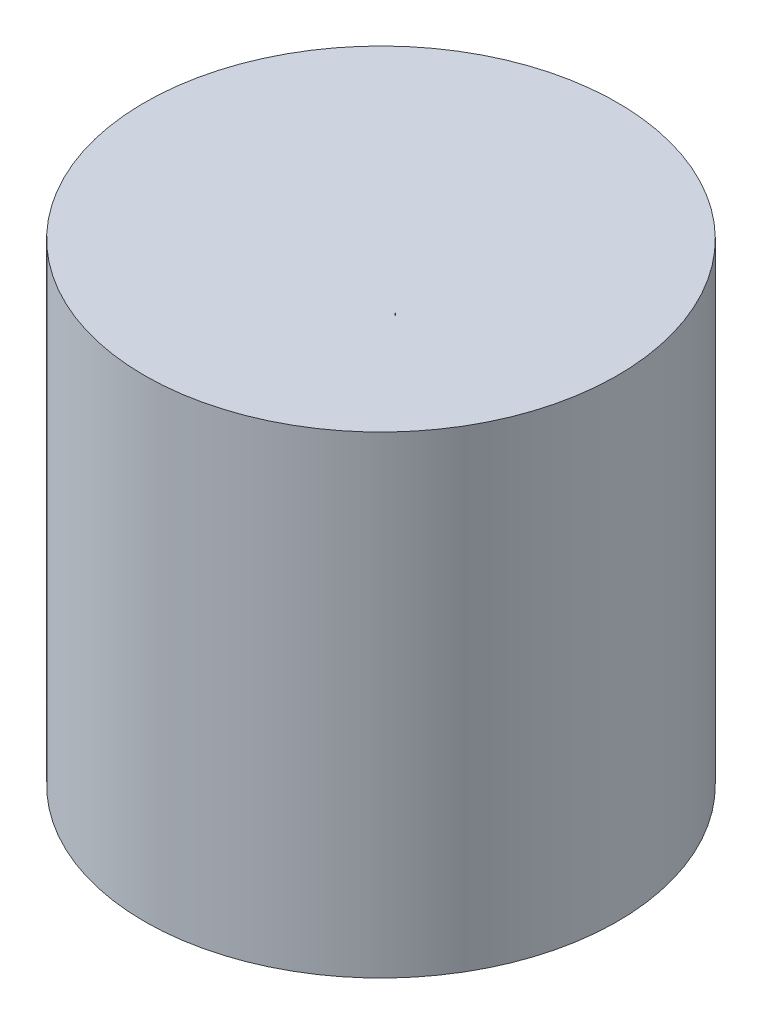
SolidWorks part; units mm, degrees
ref_plane "Front Plane" through (0, 0, 0) normal (0, 0, 1) x (1, 0, 0)
ref_plane "Top Plane" through (0, 0, 0) normal (0, 1, 0) x (1, 0, 0)
ref_plane "Right Plane" through (0, 0, 0) normal (1, 0, 0) x (0, 0, -1)
sketch "Sketch2" plane through (0, 0, 0) normal (0, 1, 0) x (1, 0, 0)
  line L0 (0.1758, -2.2335) -> (0.1763, -2.2335)
  line L2 (-2.1888, 2.9614) -> (-2.1888, -2.2335)
  line L4 (2.2036, 2.9614) -> (2.2036, -2.2335)
  line L6 (-0.246, -2.2335) -> (-0.246, -0.4828)
  line L7 (-0.246, -0.4828) -> (0.1758, -0.4828)
  line L8 (0.1758, -2.2335) -> (0.1758, -0.4828)
  circle A0 centre (0, 0) radius 6.35
  arc A1 (-2.1888, -2.2335) -> (-0.246, -2.2335) centre (-1.2174, -2.2335) ccw
  arc A2 (1.9674, -1.5831) -> (1.8844, -1.495) centre (1.19, -2.2335) ccw
  arc A3 (2.2036, 2.9614) -> (-2.1888, 2.9614) centre (0.0074, 2.9614) ccw
  circle A4 centre (0, 0) radius 5.9965
  arc A5 (0.1763, -2.2335) -> (2.2036, -2.2335) centre (1.19, -2.2335) ccw
  ellipse E0 centre (-2.0347, 3.7698) end of major axis (-3.3587, 3.7698) minor radius 0.6277
  ellipse E1 centre (2.2036, 0.364) end of major axis (2.2036, 2.4124) minor radius 0.7602 (1.8844, -1.495) -> (1.9674, -1.5831) ccw
  ellipse E2 centre (2.2036, 0.364) end of major axis (2.2036, 2.4124) minor radius 0.7602 (2.2036, -1.6845) -> (2.2036, 2.4124) ccw
  dimension "D1" = 12.7
extrude "Boss-Extrude5" add sketch "Sketch2" along normal blind 12.7 contours A0 A4 region at (-6.1704, 0, 0)
extrude "Boss-Extrude6" add sketch "Sketch2<5>" along normal blind 2.54 contours A4 E2 L4 A5 L0 L8 L7 L6 A1 L2 A3 E0 | E0 A3 L2 A1 L6 L7 L8 L0 A5 L4 E1 A2 | A3 E0 | A3 E0 | L4 E2 region at (0.0702, 0, -0.8225) region at (2.5265, 0, -0.364) region at (-1.4642, 0, -3.7178) region at (-2.567, 0, -3.8183) region at (-5.8269, 0, 0)
sketch "Sketch2<5>" plane through (0, 0, 0) normal (0, 1, 0) x (1, 0, 0) same geometry as "Sketch2"
extrude "Boss-Extrude7" add sketch "Sketch2<6>" along normal blind 3.81 contours L4 E2 region at (2.5265, 0, -0.364)
sketch "Sketch2<6>" plane through (0, 0, 0) normal (0, 1, 0) x (1, 0, 0) same geometry as "Sketch2"
extrude "Boss-Extrude8" add sketch "Sketch2<7>" along normal blind 5.08 contours E0 A3 L2 A1 L6 L7 L8 L0 A5 L4 E1 A2 region at (0.0702, 0, -0.8225)
sketch "Sketch2<7>" plane through (0, 0, 0) normal (0, 1, 0) x (1, 0, 0) same geometry as "Sketch2"
extrude "Boss-Extrude9" add sketch "Sketch2<8>" along normal blind 6.35 contours A3 E0 | A3 E0 region at (-1.4642, 0, -3.7178) region at (-2.567, 0, -3.8183)
sketch "Sketch2<8>" plane through (0, 0, 0) normal (0, 1, 0) x (1, 0, 0) same geometry as "Sketch2"
extrude "Boss-Extrude12" add sketch "Sketch2<9>" along normal blind 12.7 contours A4 E2 L4 A5 L0 L8 L7 L6 A1 L2 A3 E0 | L4 E2 | E0 A3 L2 A1 L6 L7 L8 L0 A5 L4 E1 A2 | A3 E0 | A3 E0 region at (0.0702, 0, -0.8225) region at (2.5265, 0, -0.364) region at (-1.4642, 0, -3.7178) region at (-2.567, 0, -3.8183) region at (-5.8269, 0, 0)
sketch "Sketch2<9>" plane through (0, 0, 0) normal (0, 1, 0) x (1, 0, 0) same geometry as "Sketch2"
